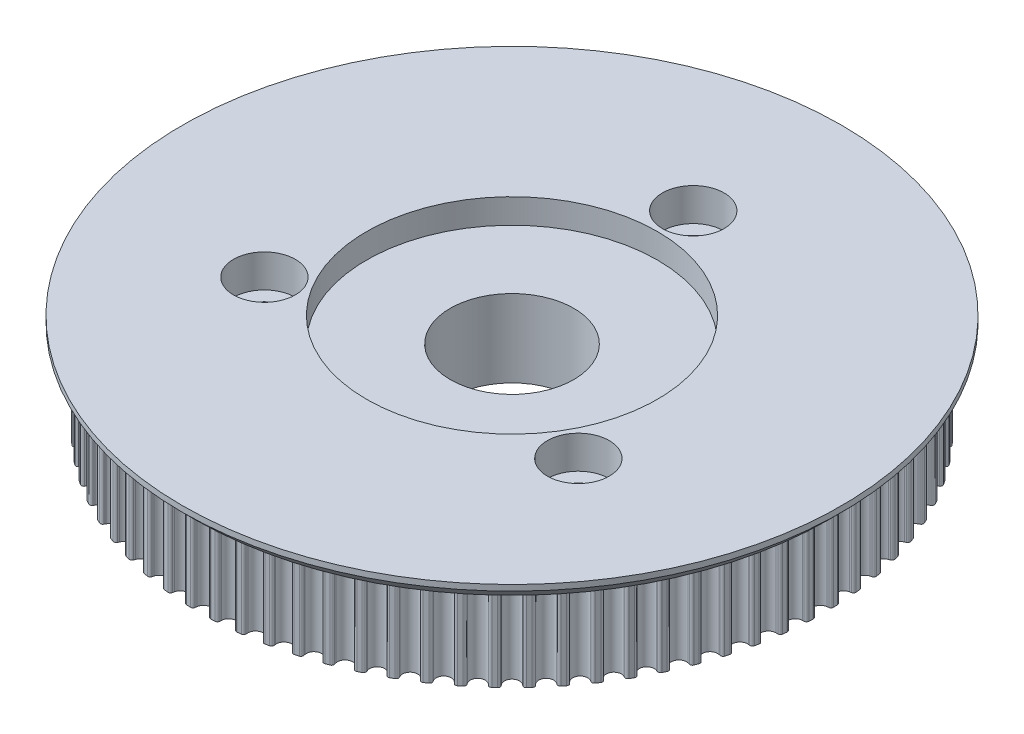
SolidWorks part; units mm, degrees
ref_plane "Front Plane" through (0, 0, 0) normal (0, 0, 1) x (1, 0, 0)
ref_plane "Top Plane" through (0, 0, 0) normal (0, 1, 0) x (1, 0, 0)
ref_plane "Right Plane" through (0, 0, 0) normal (1, 0, 0) x (0, 0, -1)
sketch "Sketch1" plane through (0, 0, 0) normal (0, 1, 0) x (1, 0, 0)
  circle A0 centre (0, 0) radius 37.815
  dimension "D1" = 75.63
extrude "Boss-Extrude1" add sketch "Sketch1" along normal blind 10.2
sketch "Sketch2" plane through (0, 0, 0) normal (0, -1, 0) x (1, 0, 0)
  line L0 (0, 37.815) -> (0, 0) construction
  line L1 (-0.9032, 37.3341) -> (-1.0564, 38.5817) construction
  line L2 (0.9032, 37.3341) -> (1.8214, 44.812) construction
  line L3 (0, 0) -> (-1.4846, 37.7858) construction
  line L4 (0, 0) -> (1.4846, 37.7858) construction
  line L5 (-0.9275, 37.5315) -> (-0.9032, 37.3341)
  line L6 (0.9032, 37.3341) -> (0.9275, 37.5315)
  line L7 (-1.4846, 37.7858) -> (0, 42.815)
  line L8 (0, 42.815) -> (1.4846, 37.7858)
  circle A0 centre (0, 0) radius 37.815 construction
  arc A1 (-0.9032, 37.3341) -> (0.9032, 37.3341) centre (0, 37.445) ccw
  arc A2 (-0.9275, 37.5315) -> (-1.235, 37.7948) centre (-1.2252, 37.495) ccw
  arc A3 (0.9275, 37.5315) -> (1.235, 37.7948) centre (1.2252, 37.495) cw
  arc A4 (1.235, 37.7948) -> (1.4846, 37.7858) centre (0, 0) cw
  arc A5 (-1.235, 37.7948) -> (-1.4846, 37.7858) centre (0, 0) ccw
  dimension "D1" = 0.91
  dimension "D4" = 0.3
  dimension "D7" = 0.3
  dimension "D2" = 0.37
  dimension "D3" = 14
  dimension "D5" = 4.5
  dimension "D6" = 2.25
  dimension "D8" = 5
extrude "Cut-Extrude1" cut sketch "Sketch2" against normal blind 10.2
pattern_circular "CirPattern1" count 80 over 360 about axis through (0, 0, 0) along (0, 1, 0) of "Cut-Extrude1"
sketch "Sketch4" plane through (0, 10.2, 0) normal (0, 1, 0) x (1, 0, 0)
  circle A0 centre (0, 0) radius 40
  dimension "D1" = 80
extrude "Boss-Extrude2" add sketch "Sketch4" along normal blind 2.2
sketch "Sketch5" plane through (0, 12.4, 0) normal (0, 1, 0) x (1, 0, 0)
  circle A0 centre (0, 0) radius 7.5
  dimension "D1" = 15
extrude "Cut-Extrude2" cut sketch "Sketch5" against normal through all
chamfer "Chamfer1" distance 1.5 angle 45 1 edges at (0, 10.2, 40)
sketch "Sketch6" plane through (0, 12.4, 0) normal (0, 1, 0) x (1, 0, 0)
  circle A0 centre (0, 22) radius 2
  circle A1 centre (0, 0) radius 7.5 construction
  circle A2 centre (19.0526, -11) radius 2
  circle A3 centre (-19.0526, -11) radius 2
  point P11 (0, 0)
  dimension "D1" = 4
  dimension "D2" = 22
  dimension "D3" = 3
extrude "Cut-Extrude3" cut sketch "Sketch6" against normal through all
sketch "Sketch7" plane through (0, 12.4, 0) normal (0, 1, 0) x (1, 0, 0)
  circle A0 centre (0, 22) radius 3.75
  circle A1 centre (19.0526, -11) radius 3.75
  circle A2 centre (-19.0526, -11) radius 3.75
  dimension "D1" = 7.5
  dimension "D2" = 7.5
  dimension "D3" = 7.5
extrude "Cut-Extrude4" cut sketch "Sketch7" against normal blind 4
sketch "Sketch8" plane through (0, 12.4, 0) normal (0, 1, 0) x (1, 0, 0)
  circle A0 centre (0, 0) radius 17.65
  dimension "D1" = 35.3
extrude "Cut-Extrude5" cut sketch "Sketch8" against normal blind 3
